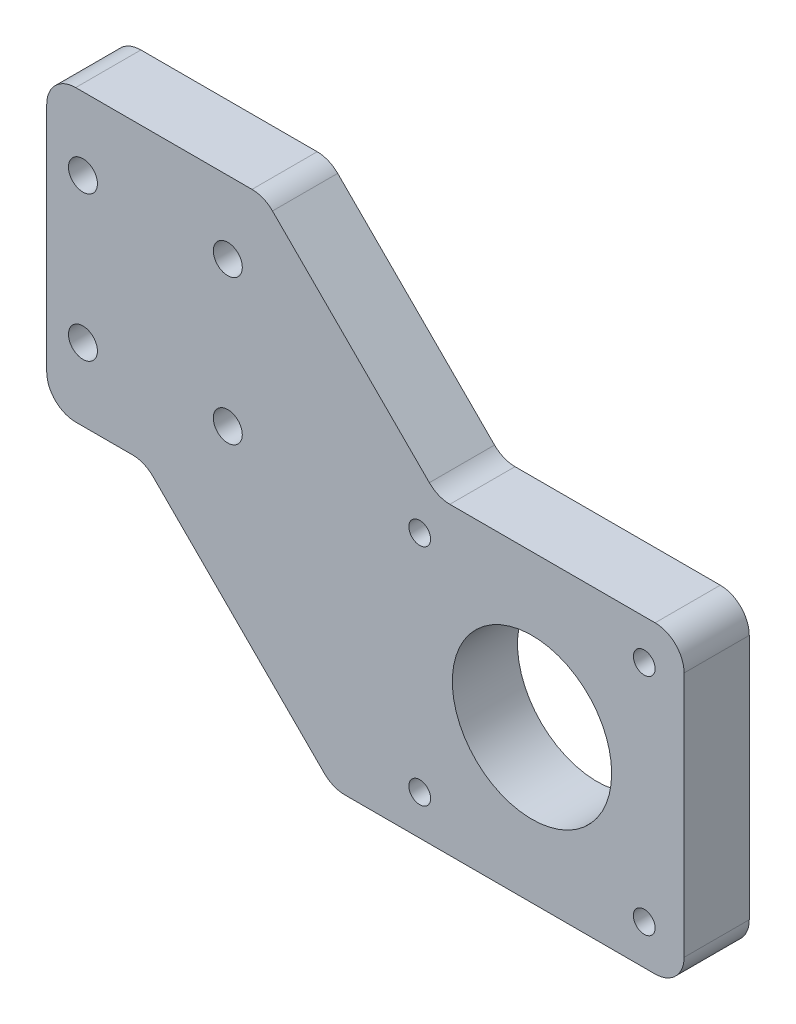
SolidWorks part; units mm, degrees
ref_plane "Front" through (0, 0, 0) normal (0, 0, 1) x (1, 0, 0)
ref_plane "Top" through (0, 0, 0) normal (0, 1, 0) x (1, 0, 0)
ref_plane "Right" through (0, 0, 0) normal (1, 0, 0) x (0, 0, -1)
sketch "Esquisse1" plane through (0, 0, 0) normal (0, 0, 1) x (1, 0, 0)
  line L1 (0, 0) -> (88, 0)
  line L2 (0, 0) -> (0, 96)
  line L3 (0, 96) -> (88, 96)
  line L4 (88, 0) -> (88, 96)
  dimension "D1" = 96
  dimension "D2" = 88
extrude "Boss.-Extru.1" add sketch "Esquisse1" along normal blind 9
sketch "Esquisse2" plane through (0, 0, 9) normal (0, 0, 1) x (1, 0, 0)
  line L0 (0, 48) -> (5, 48) construction
  line L1 (0, 96) -> (0, 0) construction
  line L2 (5, 48) -> (5, 58) construction
  line L3 (5, 48) -> (15, 48) construction
  line L4 (15, 48) -> (15, 25.2533) construction
  line L5 (25, 48) -> (25, 58) construction
  circle A0 centre (5, 58) radius 2
  circle A1 centre (5, 38) radius 2
  circle A2 centre (25, 38) radius 2
  circle A3 centre (25, 58) radius 2
  dimension "D3" = 4
  dimension "D1" = 20
  dimension "D2" = 5
  dimension "D4" = 20
extrude "Enlèv. mat.-Extru.1" cut sketch "Esquisse2" against normal through all
sketch "Esquisse3" plane through (0, 0, 9) normal (0, 0, 1) x (1, 0, 0)
  line L0 (67, 96) -> (67, 0) construction
  line L1 (88, 96) -> (0, 96) construction
  line L2 (0, 0) -> (88, 0) construction
  line L3 (67, 23) -> (75.7886, 23) construction
  line L4 (25, 38) -> (25, 58) construction
  line L5 (25, 48) -> (33.6252, 48) construction
  circle A0 centre (82.5, 38.5) radius 1.5
  circle A1 centre (82.5, 7.5) radius 1.5
  circle A2 centre (51.5, 7.5) radius 1.5
  circle A3 centre (51.5, 38.5) radius 1.5
  circle A4 centre (25, 58) radius 2 construction
  circle A5 centre (67, 23) radius 11
  dimension "D1" = 3
  dimension "D2" = 31
  dimension "D3" = 31
  dimension "D5" = 22
  dimension "D4" = 42
  dimension "D6" = 25
extrude "Enlèv. mat.-Extru.2" cut sketch "Esquisse3" against normal through all
sketch "Esquisse4" plane through (0, 0, 9) normal (0, 0, 1) x (1, 0, 0)
  line L0 (88, 0) -> (88, 96) construction
  line L1 (0, 96) -> (88, 96)
  line L2 (0, 96) -> (0, 68)
  line L3 (0, 68) -> (88, 68)
  line L4 (88, 96) -> (88, 68)
  circle A0 centre (5, 58) radius 2 construction
  dimension "D1" = 10
extrude "Enlèv. mat.-Extru.3" cut sketch "Esquisse4" against normal through all
sketch "Esquisse5" plane through (0, 0, 9) normal (0, 0, 1) x (1, 0, 0)
  line L0 (30, 68) -> (54, 44)
  line L1 (0, 68) -> (88, 68) construction
  line L2 (54, 44) -> (88, 44)
  line L3 (88, 0) -> (88, 68) construction
  line L5 (30, 68) -> (88, 68)
  line L6 (88, 68) -> (88, 44)
  circle A0 centre (25, 58) radius 2 construction
  circle A1 centre (82.5, 38.5) radius 1.5 construction
  dimension "D1" = 5.5
  dimension "D2" = 135
  dimension "D3" = 5
extrude "Enlèv. mat.-Extru.4" cut sketch "Esquisse5" against normal up to vertex (9 mm away) up to point (88, 68, 0)
sketch "Esquisse6" plane through (0, 0, 9) normal (0, 0, 1) x (1, 0, 0)
  line L1 (0, 0) -> (41.5, 0)
  line L2 (0, 0) -> (0, 28)
  line L3 (0, 28) -> (41.5, 28)
  line L4 (41.5, 0) -> (41.5, 28)
  circle A0 centre (5, 38) radius 2 construction
  circle A1 centre (51.5, 7.5) radius 1.5 construction
  dimension "D1" = 10
  dimension "D2" = 10
extrude "Enlèv. mat.-Extru.5" cut sketch "Esquisse6" against normal through all
sketch "Esquisse7" plane through (0, 0, 9) normal (0, 0, 1) x (1, 0, 0)
  line L0 (88, 0) -> (88, 44) construction
  line L1 (41.5, 0) -> (88, 0)
  line L2 (41.5, 0) -> (41.5, 2)
  line L3 (41.5, 2) -> (88, 2)
  line L4 (88, 0) -> (88, 2)
  circle A0 centre (82.5, 7.5) radius 1.5 construction
  dimension "D1" = 5.5
extrude "Enlèv. mat.-Extru.6" cut sketch "Esquisse7" against normal through all
chamfer "Chanfrein1" distance 28 angle 45 1 edges at (41.5, 28, 4.5)
fillet "Congé1" radius 4 8 edges at (88, 44, 4.5) (54, 44, 4.5) (30, 68, 4.5) (0, 68, 4.5) (13.5, 28, 4.5) (0, 28, 4.5) (88, 2, 4.5) (39.5, 2, 4.5)
